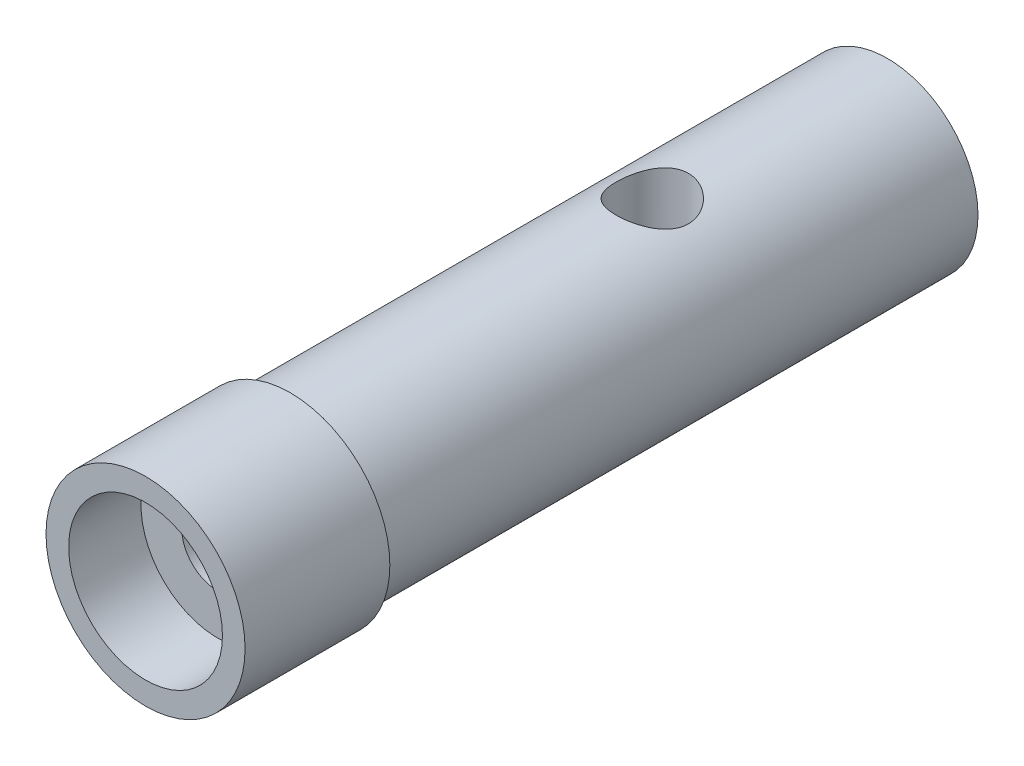
SolidWorks part; units mm, degrees
ref_plane "Front Plane" through (0, 0, 0) normal (0, 0, 1) x (1, 0, 0)
ref_plane "Top Plane" through (0, 0, 0) normal (0, 1, 0) x (1, 0, 0)
ref_plane "Right Plane" through (0, 0, 0) normal (1, 0, 0) x (0, 0, -1)
sketch "Sketch1" plane through (0, 0, 0) normal (0, 1, 0) x (1, 0, 0)
  line L0 (5.5, 0) -> (0, 0)
  line L1 (0, 0) -> (0, -8)
  line L2 (0, -8) -> (5.5, -8)
  line L3 (5.5, -8) -> (5.5, 0)
  line L4 (0, 0) -> (0, -8) construction
revolve "Revolve1" add sketch "Sketch1" angle 360 about L4 reverse direction yes
sketch "Sketch2" plane through (0, 0, 0) normal (0, 0, -1) x (-1, 0, 0)
  circle A0 centre (0, 0) radius 5
  dimension "D1" = 10
extrude "Boss-Extrude1" add sketch "Sketch2" along normal blind 33
hole_wizard "CBORE for M3.5 Hex Head Machine Screw1" positions "Sketch4" profile "Sketch3" counterbore size "M3.5" standard "ANSI Metric"
sketch "Sketch4" plane through (0, 0, 8) normal (0, 0, 1) x (1, 0, 0)
  point P0 (0, 0)
sketch "Sketch3" plane through (0, 0, 8) normal (1, 0, 0) x (0, -1, 0)
  line L0 (0, 0) -> (0, 14)
  line L1 (0, 14) -> (2, 14)
  line L2 (2, 14) -> (2, 4)
  line L3 (2, 4) -> (4.25, 4)
  line L4 (4.25, 4) -> (4.25, 0)
  line L5 (4.25, 0) -> (0, 0)
  line L10 (0, 14) -> (-2, 14) construction
  line L11 (0, -6.35) -> (0, 107.95) construction
  dimension "Hole Dia." = 4
  dimension "Hole Depth" = 14
  dimension "C'Bore Dia." = 8.5
  dimension "C'Bore Depth" = 4
  dimension "Drill Angle" = 180
hole_wizard "Hole1" positions "3DSketch1" profile "Sketch5" legacy end condition up to next
sketch3d "3DSketch1"
  point P0 (-5.5, 0, 1.5)
sketch "Sketch5" plane through (-5.5, 0, 1.5) normal (0, 1, 0) x (0, 0, 1)
  line L0 (0, 0) -> (0, 3.5)
  line L1 (0, 3.5) -> (1, 3.5)
  line L2 (1, 3.5) -> (1, 0)
  line L3 (1, 0) -> (0, 0)
  line L4 (0, 110) -> (0, -10) construction
  dimension "Diameter" = 2
  dimension "Depth" = 3.5
sketch "Sketch6" plane through (0, 0, -33) normal (0, 0, -1) x (-1, 0, 0)
  circle A0 centre (0, 0) radius 2
  circle A1 centre (0, 0) radius 5
  dimension "D1" = 4
  dimension "D2" = 10
extrude "Cut-Extrude1" cut sketch "Sketch6" against normal blind 10 contours A0
ref_plane "Plane1" through (0, 5, 0) normal (0, 1, 0) x (1, 0, 0)
sketch "Sketch7" plane through (0, 5, 0) normal (0, 1, 0) x (1, 0, 0)
  line L0 (5, 33) -> (-5, 33) construction
  circle A0 centre (0, 20) radius 2
  dimension "D1" = 4
  dimension "D2" = 13
extrude "Cut-Extrude2" cut sketch "Sketch7" against normal blind 5
